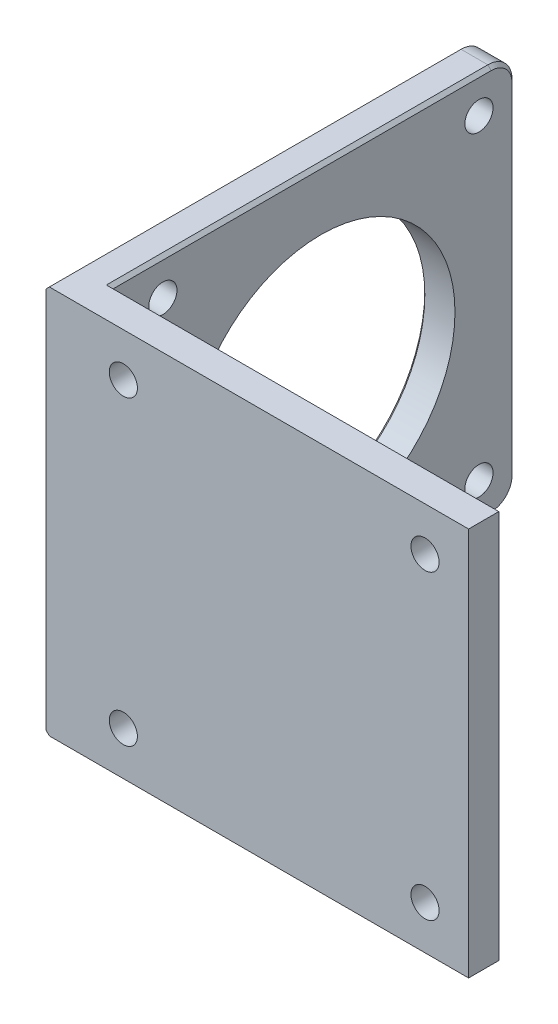
SolidWorks part; units mm, degrees
material "6061-T6 (SS)"
ref_plane "Front Plane" through (0, 0, 0) normal (0, 0, 1) x (1, 0, 0)
ref_plane "Top Plane" through (0, 0, 0) normal (0, 1, 0) x (1, 0, 0)
ref_plane "Right Plane" through (0, 0, 0) normal (1, 0, 0) x (0, 0, -1)
sketch "Sketch2" plane through (0, 0, 0) normal (0, 1, 0) x (1, 0, 0)
  line L0 (0, 0) -> (0, 65)
  line L1 (0, 65) -> (5, 65)
  line L2 (5, 65) -> (5, 5)
  line L3 (5, 5) -> (63.031, 5)
  line L4 (63.031, 5) -> (63.031, 0)
  line L5 (63.031, 0) -> (0, 0)
  dimension "D1" = 5
  dimension "D2" = 65
extrude "Boss-Extrude2" add sketch "Sketch2" along normal blind 58
sketch "Sketch3" plane through (5, 0, 0) normal (-1, 0, 0) x (0, 0, 1)
  line L0 (-65, 29) -> (-5, 29) construction
  line L1 (-65, 58) -> (-65, 0) construction
  line L24 (-5, 0) -> (-5, 58) construction
  line L25 (-65, 0) -> (0, 0) construction
  line L26 (-65, 58) -> (0, 58) construction
  line L27 (-5, 58) -> (-5, 0) construction
  circle A0 centre (-36, 29) radius 20
  point P49 (-36, 29)
  dimension "D3" = 40
  dimension "D1" = 29
extrude "Cut-Extrude3" cut sketch "Sketch3" along normal through all
sketch "Sketch5" plane through (0, 0, 0) normal (0, 0, -1) x (-1, 0, 0)
  line L0 (-56.531, 29) -> (-63.031, 29) construction
  line L1 (-63.031, 58) -> (-63.031, 0) construction
  line L2 (-34.031, 6.5) -> (-34.031, 0) construction
  line L3 (0, 0) -> (-63.031, 0) construction
  line L7 (-56.531, 6.5) -> (-11.531, 6.5) construction
  line L8 (-56.531, 6.5) -> (-56.531, 51.5) construction
  line L9 (-56.531, 51.5) -> (-11.531, 51.5) construction
  line L10 (-11.531, 6.5) -> (-11.531, 51.5) construction
  line L11 (-56.531, 6.5) -> (-11.531, 51.5) construction
  line L12 (-56.531, 51.5) -> (-11.531, 6.5) construction
  point P12 (-34.031, 29)
  point P18 (-11.531, 6.5)
  point P19 (-11.531, 51.5)
  point P20 (-56.531, 51.5)
  point P21 (-56.531, 6.5)
  dimension "D1" = 45
  dimension "D2" = 45
hole_wizard "M5x0.8 Tapped Hole3" positions "Sketch20" profile "Sketch19" tap size "M5x0.8" standard "ANSI Metric" end condition through all
sketch "Sketch20" plane through (0, 0, 0) normal (0, 0, 1) x (1, 0, 0)
  point P0 (11.531, 6.5)
  point P3 (11.531, 51.5)
  point P6 (56.531, 51.5)
  point P9 (56.531, 6.5)
sketch "Sketch19" plane through (11.531, 6.5, 0) normal (1, 0, 0) x (0, -1, 0)
  line L0 (0, 0) -> (0, 65)
  line L1 (0, 65) -> (2.1, 65)
  line L2 (2.1, 65) -> (2.1, 0)
  line L5 (2.1, 0) -> (0, 0)
  line L11 (0, -6.35) -> (0, 107.95) construction
  dimension "Thru Tap Drill Dia." = 4.2
  dimension "Thru Tap Drill Depth" = 65
cosmetic thread "Hole Thread9" parameters "D2"=5
cosmetic thread "Hole Thread10" parameters "D2"=5
cosmetic thread "Hole Thread11" parameters "D2"=5
cosmetic thread "Hole Thread12" parameters "D2"=5
sketch "Sketch6" plane through (0, 0, 0) normal (1, 0, 0) x (0, 0, -1)
  line L1 (12.4268, 5.4268) -> (59.5732, 5.4268) construction
  line L2 (12.4268, 5.4268) -> (12.4268, 52.5732) construction
  line L3 (12.4268, 52.5732) -> (59.5732, 52.5732) construction
  line L4 (59.5732, 5.4268) -> (59.5732, 52.5732) construction
  line L5 (12.4268, 5.4268) -> (59.5732, 52.5732) construction
  line L6 (12.4268, 52.5732) -> (59.5732, 5.4268) construction
  circle A0 centre (36, 29) radius 33.3375 construction
  point P0 (36, 29)
  point P7 (12.4268, 52.5732)
  point P8 (59.5732, 52.5732)
  point P9 (59.5732, 5.4268)
  point P10 (12.4268, 5.4268)
  dimension "D1" = 66.675
hole_wizard "M5x0.8 Tapped Hole2" positions "Sketch14" profile "Sketch13" tap size "M5x0.8" standard "ANSI Metric" end condition through all
sketch "Sketch14" plane through (0, 0, 0) normal (-1, 0, 0) x (0, 0, 1)
  point P0 (-12.4268, 5.4268)
  point P3 (-12.4268, 52.5732)
  point P6 (-59.5732, 52.5732)
  point P9 (-59.5732, 5.4268)
sketch "Sketch13" plane through (0, 5.4268, -12.4268) normal (0, 1, 0) x (0, 0, 1)
  line L0 (0, 0) -> (0, 63.031)
  line L1 (0, 63.031) -> (2.1, 63.031)
  line L2 (2.1, 63.031) -> (2.1, 0)
  line L5 (2.1, 0) -> (0, 0)
  line L11 (0, -6.35) -> (0, 107.95) construction
  dimension "Thru Tap Drill Dia." = 4.2
  dimension "Thru Tap Drill Depth" = 63.031
cosmetic thread "Hole Thread5" parameters "D2"=5
cosmetic thread "Hole Thread6" parameters "D2"=5
cosmetic thread "Hole Thread7" parameters "D2"=5
cosmetic thread "Hole Thread8" parameters "D2"=5
fillet "Fillet1" radius 3.6 2 edges at (2.5, 58, -65) (2.5, 0, -65)
chamfer "Chamfer1" distance 0.5 angle 45 14 edges at (0, 58, -30.7) (0, 56.9456, -63.9456) (0, 29, -65) (0, 1.0544, -63.9456) (0, 0, -30.7) (5, 58, -33.2) (5, 56.9456, -63.9456) (5, 29, -65) (5, 1.0544, -63.9456) (34.0155, 58, -5) (63.031, 29, -5) (34.0155, 0, -5) (5, 0, -33.2) (0, 29, -16)
